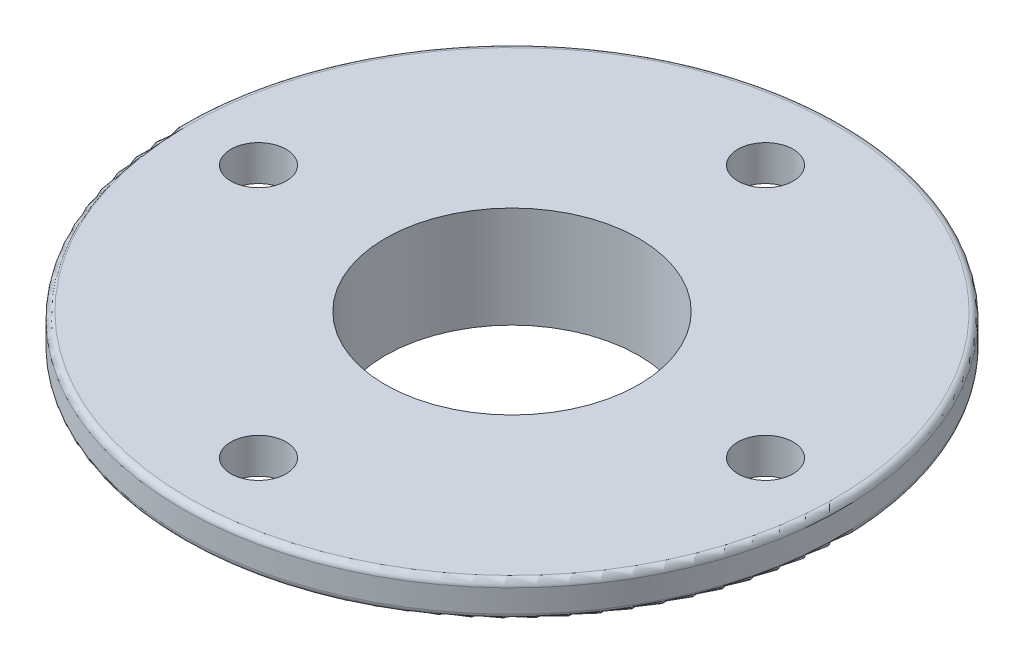
SolidWorks part; units mm, degrees
ref_plane "Front" through (0, 0, 0) normal (0, 0, 1) x (1, 0, 0)
ref_plane "Top" through (0, 0, 0) normal (0, 1, 0) x (1, 0, 0)
ref_plane "Right" through (0, 0, 0) normal (1, 0, 0) x (0, 0, -1)
sketch "Sketch1" plane through (0, 0, 0) normal (0, 1, 0) x (1, 0, 0)
  circle A0 centre (0, 0) radius 5
  circle A1 centre (0, 0) radius 7
  dimension "D1" = 10
  dimension "D2" = 14
extrude "Boss-Extrude1" add sketch "Sketch1" along normal blind 2.6
ref_plane "Plane1" through (0, 2.6, 0) normal (0, 1, 0) x (1, 0, 0)
sketch "Sketch2" plane through (0, 2.6, 0) normal (0, 1, 0) x (1, 0, 0)
  circle A0 centre (0, 0) radius 13
  circle A1 centre (0, 0) radius 5
  circle A2 centre (0, 0) radius 5 construction
  dimension "D2" = 26
extrude "Boss-Extrude2" add sketch "Sketch2" along normal blind 1.4
sketch "Sketch3" plane through (0, 4, 0) normal (0, 1, 0) x (1, 0, 0)
  line L0 (0, 0) -> (0, 13) construction
  circle A0 centre (0, 0) radius 13 construction
  circle A1 centre (0, 10) radius 1.09
  dimension "D1" = 2.18
  dimension "D2" = 10
extrude "Cut-Extrude1" cut sketch "Sketch3" against normal through all
pattern_circular "CirPattern1" count 4 over 360 about axis through (0, 2.6, 0) along (0, -1, 0) of "Cut-Extrude1"
fillet "Fillet1" radius 0.25 2 edges at (0, 4, 13) (0, 2.6, 13)
